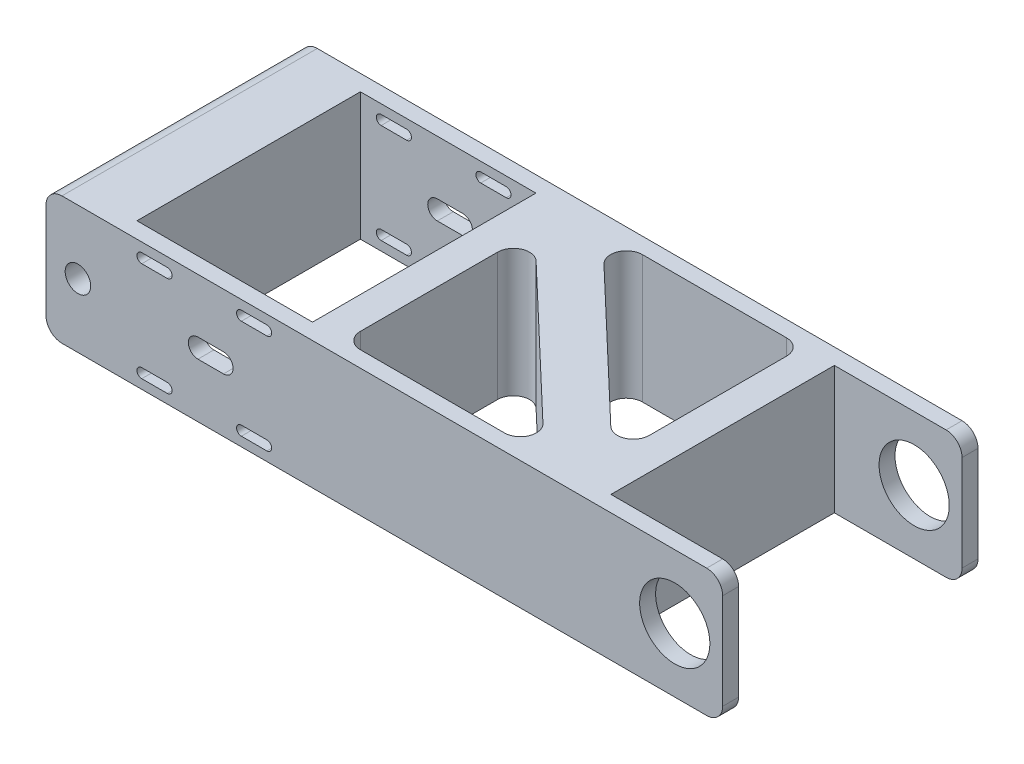
SolidWorks part; units mm, degrees
ref_plane "Front Plane" through (0, 0, 0) normal (0, 0, 1) x (1, 0, 0)
ref_plane "Top Plane" through (0, 0, 0) normal (0, 1, 0) x (1, 0, 0)
ref_plane "Right Plane" through (0, 0, 0) normal (1, 0, 0) x (0, 0, -1)
sketch "Sketch1" plane through (0, 0, 0) normal (0, 0, 1) x (1, 0, 0)
  line L0 (-106, -20) -> (-106, 20)
  line L1 (-106, 20) -> (106, 20)
  line L3 (-106, -20) -> (106, -20)
  line L4 (106, 20) -> (106, -20)
  line L5 (-106, 20) -> (106, -20) construction
  line L6 (-106, -20) -> (106, 20) construction
  line L7 (-76, 15.6) -> (-76, -15.6) construction
  line L8 (-76, 15.6) -> (-40.8, 15.6)
  line L9 (-76, 15.6) -> (-68, 15.6) construction
  line L10 (-76, 17.1) -> (-68, 17.1)
  line L11 (-76, 14.1) -> (-68, 14.1)
  line L12 (-44.8, 15.6) -> (-36.8, 15.6) construction
  line L13 (-44.8, 17.1) -> (-36.8, 17.1)
  line L14 (-44.8, 14.1) -> (-36.8, 14.1)
  line L15 (-76, -15.6) -> (-68, -15.6) construction
  line L16 (-76, -14.1) -> (-68, -14.1)
  line L17 (-76, -17.1) -> (-68, -17.1)
  line L18 (-44.8, -15.6) -> (-36.8, -15.6) construction
  line L19 (-44.8, -14.1) -> (-36.8, -14.1)
  line L20 (-44.8, -17.1) -> (-36.8, -17.1)
  line L21 (-58.4, 0) -> (-50.4, 0) construction
  line L22 (-58.4, 3) -> (-50.4, 3)
  line L23 (-58.4, -3) -> (-50.4, -3)
  circle A0 centre (-96, 0) radius 4
  circle A1 centre (-76, 15.6) radius 1.5 construction
  circle A2 centre (-44.8, 15.6) radius 1.5 construction
  circle A3 centre (-76, -15.6) radius 1.5 construction
  circle A4 centre (-44.8, -15.6) radius 1.5 construction
  circle A5 centre (-58.4, 0) radius 3 construction
  circle A6 centre (91, 0) radius 11
  arc A7 (-76, 17.1) -> (-76, 14.1) centre (-76, 15.6) ccw
  arc A8 (-68, 14.1) -> (-68, 17.1) centre (-68, 15.6) ccw
  arc A9 (-44.8, 17.1) -> (-44.8, 14.1) centre (-44.8, 15.6) ccw
  arc A10 (-36.8, 14.1) -> (-36.8, 17.1) centre (-36.8, 15.6) ccw
  arc A11 (-76, -14.1) -> (-76, -17.1) centre (-76, -15.6) ccw
  arc A12 (-68, -17.1) -> (-68, -14.1) centre (-68, -15.6) ccw
  arc A13 (-44.8, -14.1) -> (-44.8, -17.1) centre (-44.8, -15.6) ccw
  arc A14 (-36.8, -17.1) -> (-36.8, -14.1) centre (-36.8, -15.6) ccw
  arc A15 (-58.4, 3) -> (-58.4, -3) centre (-58.4, 0) ccw
  arc A16 (-50.4, -3) -> (-50.4, 3) centre (-50.4, 0) ccw
  point P0 (0, 0)
  point P16 (-76, 0)
  point P22 (-72, 15.6)
  point P28 (-40.8, 15.6)
  point P34 (-72, -15.6)
  point P40 (-40.8, -15.6)
  point P46 (-58.4, 15.6)
  point P47 (-54.4, 0)
  dimension "D3" = 8
  dimension "D5" = 31.2
  dimension "D1" = 3
  dimension "D7" = 31.2
  dimension "D9" = 6
  dimension "D10" = 22
  dimension "D4" = 10
  dimension "D2" = 212
  dimension "D6" = 40
  dimension "D8" = 20
  dimension "D11" = 15
  dimension "D12" = 4
extrude "Boss-Extrude1" add sketch "Sketch1" along normal mid plane 80 contours L4 L1 L0 L3 A14 L20 A13 L19 A12 L17 A11 L16 A10 L14 A9 A8 L11 A7 L10 L13 A6 A5 A0 region at (-2.3708, 0, 0)
sketch "Sketch2" plane through (0, 0, 0) normal (0, 1, 0) x (1, 0, 0)
  line L0 (-106, 40) -> (106, 40) construction
  line L1 (-82.5, 35) -> (-27.5, 35)
  line L2 (-82.5, 35) -> (-82.5, -35)
  line L3 (-82.5, -35) -> (-27.5, -35)
  line L4 (-27.5, 35) -> (-27.5, -35)
  line L5 (-82.5, 35) -> (-27.5, -35) construction
  line L6 (-82.5, -35) -> (-27.5, 35) construction
  line L7 (-17.5, 24.6429) -> (45.125, -35)
  line L8 (106, -40) -> (106, 40) construction
  line L9 (66, 35) -> (106, 35)
  line L10 (66, 35) -> (66, -35)
  line L11 (66, -35) -> (106, -35)
  line L12 (106, 35) -> (106, -35)
  line L13 (66, 35) -> (106, -35) construction
  line L14 (66, -35) -> (106, 35) construction
  line L15 (-17.5, 35) -> (56, 35) construction
  line L16 (-17.5, 35) -> (-17.5, -35) construction
  line L17 (-17.5, -35) -> (56, -35) construction
  line L18 (56, 35) -> (56, -35) construction
  line L19 (-17.5, 35) -> (56, -35) construction
  line L20 (-17.5, -35) -> (56, 35) construction
  line L21 (-6.625, 35) -> (56, -24.6429)
  line L22 (-17.5, 24.6429) -> (-17.5, -35)
  line L23 (-6.625, 35) -> (56, 35)
  line L24 (56, 35) -> (56, -24.6429)
  line L25 (-17.5, -35) -> (45.125, -35)
  point P0 (-55, 0)
  point P10 (19.25, 0)
  point P11 (86, 0)
  point P24 (0, 0)
  dimension "D1" = 55
  dimension "D2" = 5
  dimension "D3" = 55
  dimension "D4" = 40
  dimension "D5" = 10
  dimension "D6" = 10
  dimension "D7" = 15
extrude "Cut-Extrude3" cut sketch "Sketch2" against normal through all both and the other way through all
fillet "Fillet1" radius 5 6 edges at (45.125, 0, 35) (-17.5, 0, 35) (56, 0, 24.6429) (56, 0, -35) (-6.625, 0, -35) (-17.5, 0, -24.6429)
fillet "Fillet2" radius 5 6 edges at (-106, 20, 0) (-106, -20, 0) (106, 20, 37.5) (106, -20, 37.5) (106, 20, -37.5) (106, -20, -37.5)
